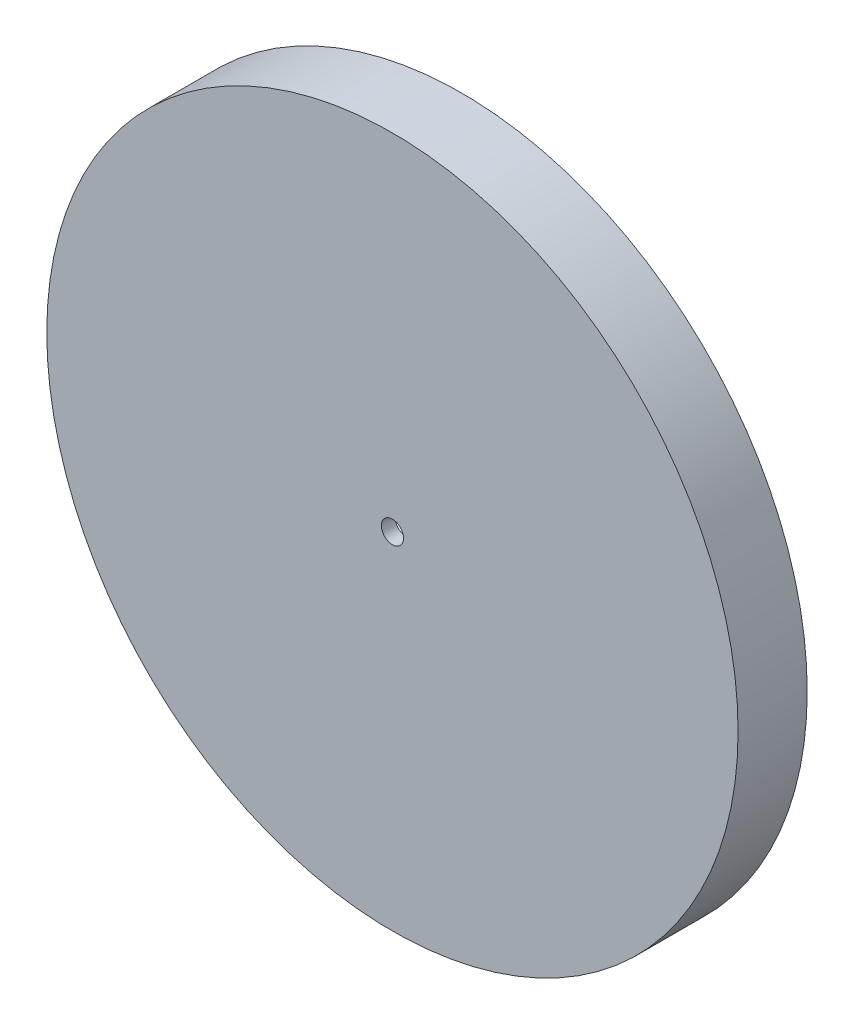
SolidWorks part; units mm, degrees
ref_plane "Front Plane" through (0, 0, 0) normal (0, 0, 1) x (1, 0, 0)
ref_plane "Top Plane" through (0, 0, 0) normal (0, 1, 0) x (1, 0, 0)
ref_plane "Right Plane" through (0, 0, 0) normal (1, 0, 0) x (0, 0, -1)
sketch "Sketch1" plane through (0, 0, 0) normal (0, 0, 1) x (1, 0, 0)
  circle A0 centre (0, 0) radius 2
  circle A1 centre (0, 0) radius 60
  circle A2 centre (0, 0) radius 62.5
  dimension "D1" = 4
  dimension "D2" = 120
  dimension "D3" = 2.5
extrude "Boss-Extrude1" add sketch "Sketch1" along normal blind 2.5 contours A1 A0 | A2 A1 region at (-58.3029, 0, 0) region at (-60.7322, 0, 0)
extrude "Boss-Extrude2" add sketch "Sketch1<3>" against normal blind 10 contours A1 | A2
sketch "Sketch1<3>" plane through (0, 0, 0) normal (0, 0, 1) x (1, 0, 0) same geometry as "Sketch1"
